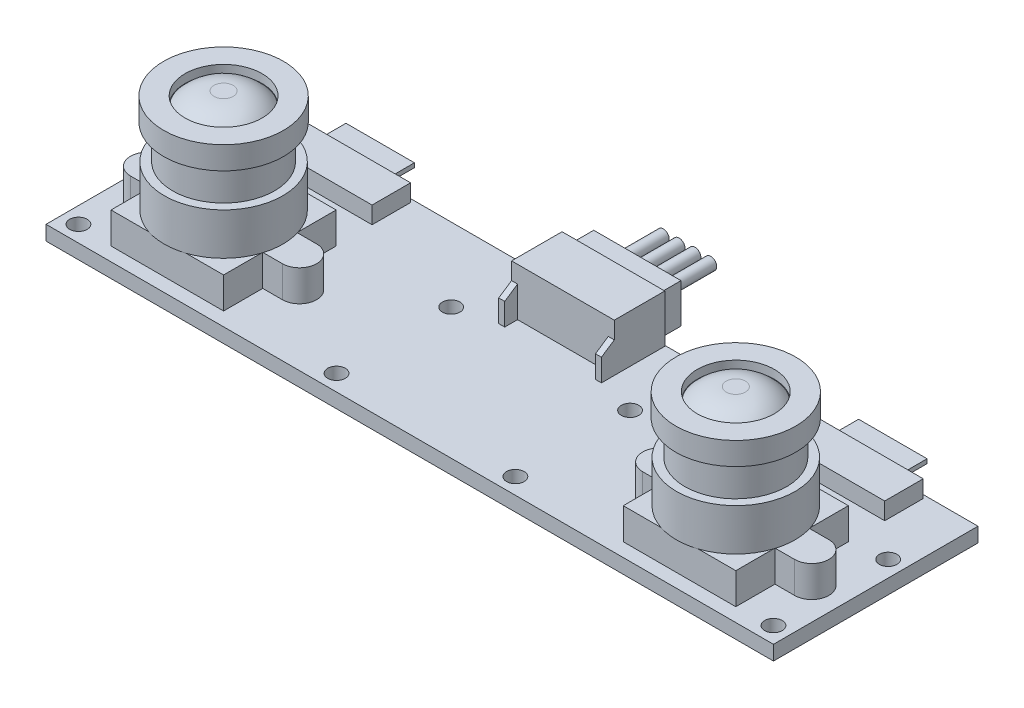
SolidWorks part; units mm, degrees
ref_plane "Front" through (0, 0, 0) normal (0, 0, 1) x (1, 0, 0)
ref_plane "Top" through (0, 0, 0) normal (0, 1, 0) x (1, 0, 0)
ref_plane "Right" through (0, 0, 0) normal (1, 0, 0) x (0, 0, -1)
sketch "Sketch1" plane through (0, 0, 0) normal (0, 1, 0) x (1, 0, 0)
  line L1 (-42.5, -11.95) -> (42.5, -11.95)
  line L2 (-42.5, -11.95) -> (-42.5, 11.95)
  line L3 (-42.5, 11.95) -> (42.5, 11.95)
  line L4 (42.5, -11.95) -> (42.5, 11.95)
  line L5 (-42.5, -11.95) -> (42.5, 11.95) construction
  line L6 (-42.5, 11.95) -> (42.5, -11.95) construction
  point P0 (0, 0)
  dimension "D1" = 23.9
  dimension "D2" = 85
extrude "Boss-Extrude1" add sketch "Sketch1" along normal blind 1.7
sketch "Sketch2" plane through (0, 1.7, 0) normal (0, 1, 0) x (1, 0, 0)
  line L0 (40.605, -11.08) -> (40.605, -11.95) construction
  line L1 (-40.605, -10.055) -> (40.605, -10.055) construction
  line L2 (-40.605, -10.055) -> (-40.605, 3.345) construction
  line L3 (-40.605, 3.345) -> (40.605, 3.345) construction
  line L5 (-40.605, -10.055) -> (40.605, 3.345) construction
  line L6 (-40.605, 3.345) -> (40.605, -10.055) construction
  line L7 (-10.45, -10.055) -> (10.45, -10.055) construction
  line L8 (-10.45, -10.055) -> (-10.45, 3.345) construction
  line L9 (-10.45, 3.345) -> (10.45, 3.345) construction
  line L10 (10.45, -10.055) -> (10.45, 3.345) construction
  line L11 (-10.45, -10.055) -> (10.45, 3.345) construction
  line L12 (-10.45, 3.345) -> (10.45, -10.055) construction
  line L14 (-42.5, -11.95) -> (42.5, -11.95) construction
  line L16 (41.63, -10.055) -> (42.5, -10.055) construction
  line L17 (42.5, -11.95) -> (42.5, 11.95) construction
  line L18 (-9.425, 3.345) -> (9.425, 3.345) construction
  line L19 (40.605, 2.32) -> (40.605, -9.03) construction
  circle A0 centre (-40.605, 3.345) radius 1.025
  circle A1 centre (-10.45, 3.345) radius 1.025
  circle A2 centre (-40.605, -10.055) radius 1.025
  circle A3 centre (-10.45, -10.055) radius 1.025
  circle A4 centre (10.45, 3.345) radius 1.025
  circle A5 centre (40.605, 3.345) radius 1.025
  circle A6 centre (40.605, -10.055) radius 1.025
  circle A7 centre (10.45, -10.055) radius 1.025
  point P0 (0, -3.355)
  point P5 (0, -3.355)
  dimension "D1" = 2.05
  dimension "D2" = 0.87
  dimension "D3" = 18.85
  dimension "D4" = 11.35
extrude "Cut-Extrude1" cut sketch "Sketch2" against normal through all
sketch "Sketch3" plane through (0, 1.7, 0) normal (0, 1, 0) x (1, 0, 0)
  line L0 (42.5, 11.95) -> (-42.5, 11.95) construction
  line L1 (-6, 5.95) -> (6, 5.95)
  line L2 (-6, 5.95) -> (-6, 11.95)
  line L3 (-6, 11.95) -> (6, 11.95)
  line L4 (6, 5.95) -> (6, 11.95)
  line L5 (-6, 5.95) -> (6, 11.95) construction
  line L6 (-6, 11.95) -> (6, 5.95) construction
  point P0 (0, 8.95)
  dimension "D1" = 12
  dimension "D2" = 6
extrude "Boss-Extrude2" add sketch "Sketch3" along normal blind 5.6
sketch "Sketch4" plane through (0, 1.7, 0) normal (0, 1, 0) x (1, 0, 0)
  line L1 (-6, 5.95) -> (-5.3, 5.95)
  line L2 (-6, 5.95) -> (-6, 4.45)
  line L3 (-6, 4.45) -> (-5.3, 4.45)
  line L4 (-5.3, 5.95) -> (-5.3, 4.45)
  line L5 (6, 5.95) -> (5.3, 5.95)
  line L6 (6, 5.95) -> (6, 4.45)
  line L7 (6, 4.45) -> (5.3, 4.45)
  line L8 (5.3, 5.95) -> (5.3, 4.45)
  dimension "D1" = 0.7
  dimension "D2" = 1.5
extrude "Boss-Extrude3" add sketch "Sketch4" along normal blind 3.6
chamfer "Chamfer1" distance 1 distance2 1.5 2 edges at (-5.65, 5.3, -4.45) (5.65, 5.3, -4.45) first distance on face at (-5.65, 3.5, -4.45) first distance on face at (5.65, 3.5, -4.45)
sketch "Sketch5" plane through (0, 0, -11.95) normal (0, 0, -1) x (-1, 0, 0)
  line L1 (6, 7.3) -> (-6, 7.3)
  line L2 (6, 7.3) -> (6, 1.7)
  line L3 (6, 1.7) -> (-6, 1.7)
  line L4 (-6, 7.3) -> (-6, 1.7)
extrude "Cut-Extrude2" cut sketch "Sketch5" against normal blind 0.1
sketch "Sketch6" plane through (0, 0, -11.85) normal (0, 0, -1) x (-1, 0, 0)
  line L1 (-5.1, 6.5) -> (5.1, 6.5)
  line L2 (-5.1, 6.5) -> (-5.1, 1.9)
  line L3 (-5.1, 1.9) -> (5.1, 1.9)
  line L4 (5.1, 6.5) -> (5.1, 1.9)
  line L5 (-42.5, 1.7) -> (42.5, 1.7) construction
  point P6 (0, 6.5)
  dimension "D1" = 10.2
  dimension "D2" = 4.6
  dimension "D3" = 0.2
extrude "Boss-Extrude4" add sketch "Sketch6" along normal blind 2.8
sketch "Sketch7" plane through (0, 0, -14.65) normal (0, 0, -1) x (-1, 0, 0)
  line L0 (-0.225, 4.2) -> (0.225, 4.2) construction
  line L1 (5.1, 1.9) -> (5.1, 6.5) construction
  line L2 (-2.075, 4.2) -> (-1.625, 4.2) construction
  line L3 (1.625, 4.2) -> (2.075, 4.2) construction
  circle A0 centre (0.925, 4.2) radius 0.7
  circle A1 centre (-0.925, 4.2) radius 0.7
  circle A2 centre (-2.775, 4.2) radius 0.7
  circle A3 centre (2.775, 4.2) radius 0.7
  point P2 (0, 4.2)
  point P7 (5.1, 4.2)
  dimension "D1" = 1.4
  dimension "D2" = 0.45
extrude "Boss-Extrude5" add sketch "Sketch7" along normal blind 5.8
sketch "Sketch8" plane through (0, 1.7, 0) normal (0, 1, 0) x (1, 0, 0)
  line L0 (0, 0) -> (0, -11.95) construction
  line L1 (-36.5, -10.35) -> (-23.35, -10.35)
  line L2 (-36.5, -10.35) -> (-36.5, -5.775)
  line L3 (-36.5, 2.8) -> (-23.35, 2.8)
  line L4 (-23.35, -10.35) -> (-23.35, -5.775)
  line L9 (-42.5, -11.95) -> (42.5, -11.95) construction
  line L10 (-36.5, -1.775) -> (-38.8, -1.775)
  line L11 (-36.5, -5.775) -> (-38.8, -5.775)
  line L12 (-36.5, -1.775) -> (-36.5, 2.8)
  line L13 (-23.35, -1.775) -> (-21.05, -1.775)
  line L14 (-23.35, -5.775) -> (-21.05, -5.775)
  line L15 (-23.35, -1.775) -> (-23.35, 2.8)
  line L16 (-42.5, 11.95) -> (-42.5, -11.95) construction
  line L17 (23.35, -1.775) -> (23.35, 2.8)
  line L18 (23.35, -5.775) -> (21.05, -5.775)
  line L19 (23.35, -1.775) -> (21.05, -1.775)
  line L20 (36.5, -1.775) -> (36.5, 2.8)
  line L21 (36.5, -5.775) -> (38.8, -5.775)
  line L22 (36.5, -1.775) -> (38.8, -1.775)
  line L23 (23.35, -10.35) -> (23.35, -5.775)
  line L24 (36.5, 2.8) -> (23.35, 2.8)
  line L25 (36.5, -10.35) -> (36.5, -5.775)
  line L26 (36.5, -10.35) -> (23.35, -10.35)
  arc A0 (-38.8, -1.775) -> (-38.8, -5.775) centre (-38.8, -3.775) ccw
  arc A1 (-21.05, -1.775) -> (-21.05, -5.775) centre (-21.05, -3.775) cw
  arc A2 (21.05, -1.775) -> (21.05, -5.775) centre (21.05, -3.775) ccw
  arc A3 (38.8, -1.775) -> (38.8, -5.775) centre (38.8, -3.775) cw
  dimension "D1" = 4
  dimension "D2" = 13.15
  dimension "D3" = 13.15
  dimension "D4" = 2.3
  dimension "D5" = 1.6
  dimension "D6" = 6
extrude "Boss-Extrude6" add sketch "Sketch8" along normal blind 3.65
sketch "Sketch9" plane through (0, 5.35, 0) normal (0, 1, 0) x (1, 0, 0)
  line L0 (-23.35, 2.8) -> (-36.5, 2.8) construction
  line L1 (36.5, 2.8) -> (23.35, 2.8) construction
  circle A0 centre (-29.925, -3.775) radius 6.925
  circle A1 centre (29.925, -3.775) radius 6.925
  arc A2 (21.05, -1.775) -> (21.05, -5.775) centre (21.05, -3.775) ccw construction
  point P8 (-29.925, 2.8)
  point P12 (29.925, 2.8)
  point P16 (19.05, -3.775)
  dimension "D1" = 13.85
extrude "Boss-Extrude7" add sketch "Sketch9" along normal blind 4.9
sketch "Sketch10" plane through (0, 10.25, 0) normal (0, 1, 0) x (1, 0, 0)
  circle A0 centre (-29.925, -3.775) radius 5.95
  circle A1 centre (29.925, -3.775) radius 5.95
  dimension "D1" = 11.9
extrude "Boss-Extrude8" add sketch "Sketch10" along normal blind 4
sketch "Sketch11" plane through (0, 14.25, 0) normal (0, 1, 0) x (1, 0, 0)
  circle A0 centre (-29.925, -3.775) radius 7
  circle A1 centre (29.925, -3.775) radius 7
  dimension "D1" = 14
extrude "Boss-Extrude9" add sketch "Sketch11" along normal blind 2.65
sketch "Sketch12" plane through (0, 16.9, 0) normal (0, 1, 0) x (1, 0, 0)
  circle A0 centre (-29.925, -3.775) radius 4.5
  circle A1 centre (29.925, -3.775) radius 4.5
  dimension "D1" = 9
extrude "Cut-Extrude3" cut sketch "Sketch12" against normal blind 1
sketch "Sketch13" plane through (0, 15.9, 0) normal (0, 1, 0) x (1, 0, 0)
  circle A0 centre (-29.925, -3.775) radius 4.45
  circle A1 centre (29.925, -3.775) radius 4.45
  dimension "D1" = 8.9
extrude "Boss-Extrude10" add sketch "Sketch13" along normal blind 1.5
fillet "Fillet1" radius 4.45 2 edges at (-29.925, 17.4, 8.225) (29.925, 17.4, 8.225)
sketch "Sketch14" plane through (0, 1.7, 0) normal (0, 1, 0) x (1, 0, 0)
  line L0 (-36.5, 9.3) -> (-42.5, 9.3) construction
  line L1 (-36.5, 11.55) -> (-23.4, 11.55)
  line L2 (-36.5, 11.55) -> (-36.5, 7.05)
  line L3 (-36.5, 7.05) -> (-23.4, 7.05)
  line L4 (-23.4, 11.55) -> (-23.4, 7.05)
  line L5 (23.4, 11.55) -> (36.5, 11.55)
  line L6 (23.4, 11.55) -> (23.4, 7.05)
  line L7 (23.4, 7.05) -> (36.5, 7.05)
  line L8 (36.5, 11.55) -> (36.5, 7.05)
  line L9 (-42.5, 11.95) -> (-42.5, -11.95) construction
  line L10 (36.5, 9.3) -> (42.5, 9.3) construction
  line L11 (42.5, -11.95) -> (42.5, 11.95) construction
  line L12 (42.5, 11.95) -> (-42.5, 11.95) construction
  dimension "D1" = 13.1
  dimension "D2" = 4.5
  dimension "D3" = 0.4
  dimension "D4" = 6
extrude "Boss-Extrude11" add sketch "Sketch14" along normal blind 2
sketch "Sketch15" plane through (0, 0, -11.55) normal (0, 0, -1) x (-1, 0, 0)
  line L0 (23.4, 3.7) -> (36.5, 3.7) construction
  line L1 (-33.95, 2.95) -> (-25.95, 2.95)
  line L2 (-33.95, 2.95) -> (-33.95, 2.45)
  line L3 (-33.95, 2.45) -> (-25.95, 2.45)
  line L4 (-25.95, 2.95) -> (-25.95, 2.45)
  line L5 (25.95, 2.95) -> (33.95, 2.95)
  line L6 (25.95, 2.95) -> (25.95, 2.45)
  line L7 (25.95, 2.45) -> (33.95, 2.45)
  line L8 (33.95, 2.95) -> (33.95, 2.45)
  line L9 (-36.5, 3.7) -> (-23.4, 3.7) construction
  line L10 (-23.4, 3.7) -> (-23.4, 1.7) construction
  point P8 (29.95, 2.95)
  point P11 (29.95, 3.7)
  point P12 (-29.95, 2.95)
  point P15 (-29.95, 3.7)
  point P18 (-25.95, 2.7)
  point P21 (-23.4, 2.7)
  dimension "D1" = 0.5
  dimension "D2" = 8
extrude "Boss-Extrude12" add sketch "Sketch15" along normal blind 3
